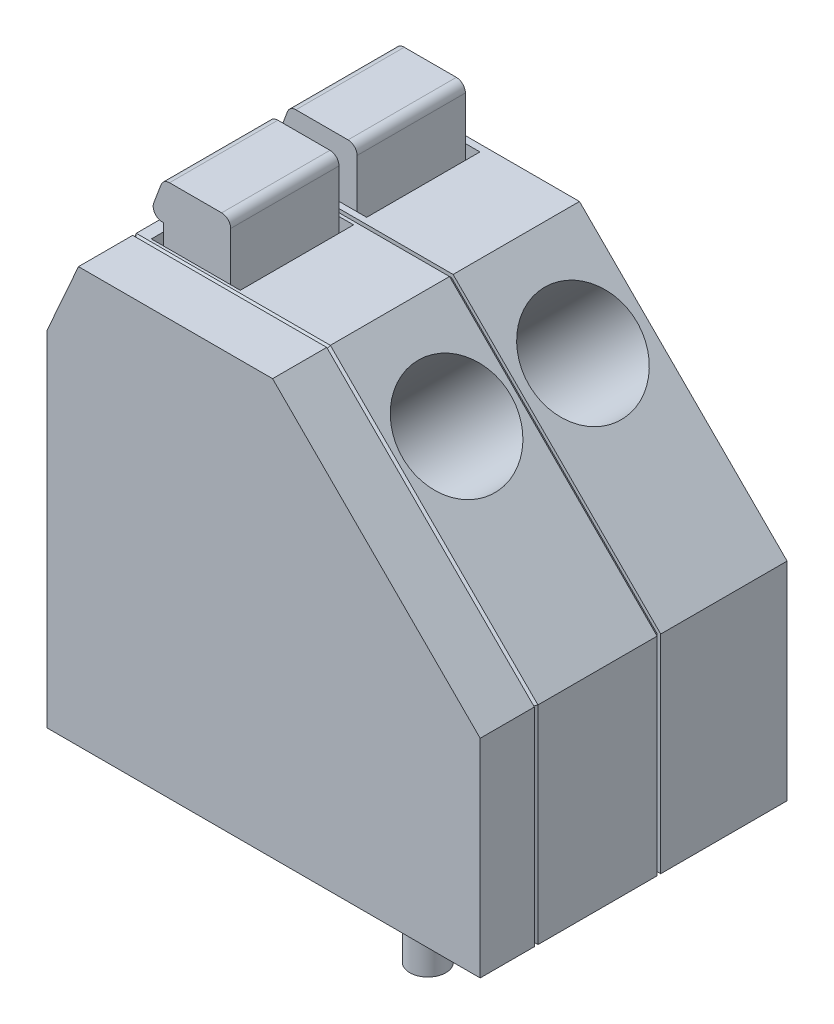
SolidWorks part; units mm, degrees
ref_plane "Front Plane" through (0, 0, 0) normal (0, 0, 1) x (1, 0, 0)
ref_plane "Top Plane" through (0, 0, 0) normal (0, 1, 0) x (1, 0, 0)
ref_plane "Right Plane" through (0, 0, 0) normal (1, 0, 0) x (0, 0, -1)
sketch "Sketch1" plane through (0, 0, 0) normal (0, 0, 1) x (1, 0, 0)
  line L0 (0, 0) -> (12, 0)
  line L1 (12, 0) -> (12, 5.75)
  line L2 (12, 5.75) -> (6.25, 11.5)
  line L3 (6.25, 11.5) -> (0.8751, 11.5)
  line L5 (0.8751, 11.5) -> (0, 9.5271)
  line L6 (0, 9.5271) -> (0, 0)
  dimension "D1" = 12
  dimension "D2" = 11.5
  dimension "D3" = 135
  dimension "D4" = 5.75
extrude "Boss-Extrude1" add sketch "Sketch1" along normal blind 3.5 contours L2 L3 L5 L6 L0 L1
sketch "Sketch2" plane through (8.875, 8.875, 0) normal (0.7071, 0.7071, 0) x (0, 0, -1)
  line L0 (-1.75, 3.7123) -> (-1.75, 1.1012) construction
  line L1 (-3.5, 3.7123) -> (0, 3.7123) construction
  circle A0 centre (-1.75, 1.1012) radius 1.5
  dimension "D1" = 3
extrude "Cut-Extrude1" cut sketch "Sketch2" against normal blind 5
sketch "Sketch3" plane through (0, 11.5, 0) normal (0, 1, 0) x (1, 0, 0)
  line L1 (1.2198, -0.1897) -> (3.6834, -0.1897)
  line L2 (1.2198, -0.1897) -> (1.2198, -3.3275)
  line L3 (1.2198, -3.3275) -> (3.6834, -3.3275)
  line L4 (3.6834, -0.1897) -> (3.6834, -3.3275)
extrude "Cut-Extrude2" cut sketch "Sketch3" against normal blind 2
sketch "Sketch5" plane through (0, 0, 3.3275) normal (0, 0, -1) x (-1, 0, 0)
  line L0 (-3.4177, 9.5) -> (-3.4177, 13.1)
  line L1 (-1.2198, 9.5) -> (-3.6834, 9.5) construction
  line L2 (-3.4177, 13.1) -> (-1.5504, 13.1)
  line L3 (-1.5504, 13.1) -> (-1.16, 12.0598)
  line L4 (-1.16, 12.0598) -> (-1.5504, 12.0598)
  line L5 (-1.5504, 12.0598) -> (-1.5504, 9.5)
  line L6 (-1.5504, 9.5) -> (-3.4177, 9.5)
  line L7 (-1.2198, 11.5) -> (-3.6834, 11.5) construction
  dimension "D1" = 1.6
extrude "Boss-Extrude2" add sketch "Sketch5" along normal blind 3 separate body
fillet "Fillet1" radius 0.25 3 edges at (1.16, 12.0598, 1.8275) (3.4177, 13.1, 1.8275) (1.5504, 13.1, 1.8275)
pattern_linear "LPattern1" count 2 spacing 3.5 along (0, 0, 1) of bodies 104 103
sketch "Sketch7" plane through (0, 0, 7) normal (0, 0, 1) x (1, 0, 0)
  line L0 (0, 9.5271) -> (0.8751, 11.5)
  line L1 (0.8751, 11.5) -> (6.25, 11.5)
  line L2 (6.25, 11.5) -> (12, 5.75)
  line L3 (12, 5.75) -> (12, 0)
  line L4 (12, 0) -> (0, 0)
  line L5 (0, 0) -> (0, 9.5271)
extrude "Boss-Extrude4" add sketch "Sketch7" along normal blind 1.5 separate body
sketch "Sketch8" plane through (0, 0, 0) normal (0, -1, 0) x (1, 0, 0)
  line L0 (0, 5.25) -> (7.3, 5.25) construction
  line L2 (0, 7) -> (0, 3.5) construction
  line L3 (0, 1.75) -> (2.3, 1.75) construction
  line L4 (0, 3.5) -> (0, 0) construction
  circle A0 centre (7.3, 5.25) radius 0.5
  circle A1 centre (2.3, 1.75) radius 0.5
  dimension "D1" = 1
  dimension "D2" = 2.3
  dimension "D3" = 5
extrude "Boss-Extrude5" add sketch "Sketch8" along normal blind 3.6 separate body
ref_point "Point1"
chamfer "Chamfer1" distance 0.1 angle 45 12 edges at (6, 0, 7) (0, 4.7635, 7) (0.4376, 10.5135, 7) (12, 2.875, 7) (3.5626, 11.5, 7) (9.125, 8.625, 7) (6, 0, 3.5) (0, 4.7635, 3.5) (0.4376, 10.5135, 3.5) (12, 2.875, 3.5) (3.5626, 11.5, 3.5) (9.125, 8.625, 3.5)
sketch "Sketch9" plane through (0, 0, 0) normal (0, 0, -1) x (-1, 0, 0)
  circle A0 centre (-7.8248, 2.6388) radius 0.7557
  circle A1 centre (-2.3626, 8.1308) radius 0.7557
  point P4 (-10.0389, 2.5737)
  point P5 (-4.5985, 6.9578)
  point P6 (-2.3626, 8.1308)
  point P7 (-7.8248, 2.6388)
extrude "Cut-Extrude3" cut sketch "Sketch9" against normal blind 0.2
